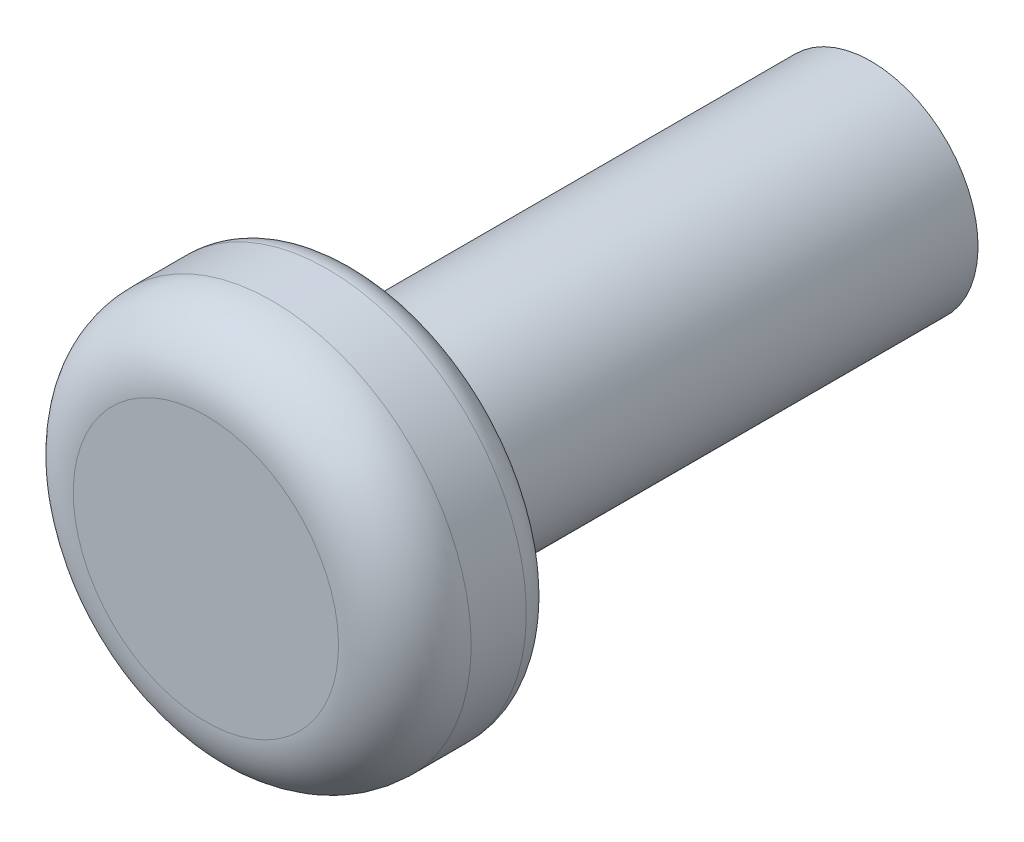
SolidWorks part; units mm, degrees
ref_plane "Front" through (0, 0, 0) normal (0, 0, 1) x (1, 0, 0)
ref_plane "Top" through (0, 0, 0) normal (0, 1, 0) x (1, 0, 0)
ref_plane "Right" through (0, 0, 0) normal (1, 0, 0) x (0, 0, -1)
sketch "Sketch0" plane through (0, 0, 0) normal (1, 0, 0) x (0, 0, -1)
  line L0 (0, 0) -> (-3.55, 0) construction
  line L1 (0, 0) -> (12, 0) construction
  line L2 (-3.55, 4.65) -> (-3.55, -4.65) construction
  line L3 (12, 2.5) -> (12, -2.5) construction
  point P6 (-3.55, 0)
  point P9 (12, 0)
sketch "Sketch1" plane through (0, 0, 0) normal (0, 0, 1) x (1, 0, 0)
  circle A0 centre (0, 0) radius 4.65
extrude "Extrude3" add sketch "Sketch1" along normal up to vertex (3.55 mm away) up to point (0, 0, 3.55)
ref_plane "Plane1" through (0, 0, 3.55) normal (0, 0, 1) x (1, 0, 0)
sketch "Sketch11" plane through (0, 0, 0) normal (1, 0, 0) x (0, 0, -1)
  line L2 (-3.55, 4.65) -> (-3.55, -4.65) construction
  line L4 (0, 4.65) -> (-3.55, 4.65) construction
  line L5 (-2, 4.65) -> (-0.71, 4.65)
  line L6 (0, -4.65) -> (0, 4.65) construction
  line L7 (-3.55, 4.65) -> (-3.55, 3.1) construction
  line L8 (-3.55, 1.55) -> (-3.55, 0) construction
  line L9 (-3.55, 3.1) -> (-3.55, 1.55) construction
  line L10 (-3.55, 3.1) -> (-3.804, 3.1)
  line L11 (0, 0) -> (-3.55, 0) construction
  line L12 (-3.804, 3.1) -> (-3.804, 4.904)
  line L13 (-3.804, 4.904) -> (0.254, 4.904)
  line L14 (0.254, 4.904) -> (0.254, 3.94)
  line L15 (0.254, 3.94) -> (0, 3.94)
  arc A0 (-3.55, 3.1) -> (-2, 4.65) centre (-2, 3.1) cw
  arc A1 (-0.71, 4.65) -> (0, 3.94) centre (-0.71, 3.94) cw
  dimension "D1" = 0.71
  dimension "D2" = 0.254
  dimension "D3" = 0.254
revolve "Cut-Revolve3" cut sketch "Sketch11" angle 360 about L11
sketch "Sketch17" plane through (0, 0, 0) normal (1, 0, 0) x (0, 0, -1)
  line L0 (12, 2.5) -> (12, -2.5) construction
  line L1 (0, 0) -> (12, 0)
  line L2 (0, 0) -> (0, 2.5)
  line L3 (0, 2.5) -> (12, 2.5)
  line L4 (12, 0) -> (12, 2.5)
revolve "Revolve1" add sketch "Sketch17" angle 360 about L11
sketch "Sketch14" plane through (0, 0, 0) normal (1, 0, 0) x (0, 0, -1)
  line L0 (0.0794, 0.5901) -> (0.1786, 0.762) construction
  line L2 (0.1786, 0.762) -> (0.2183, 0.762)
  line L3 (0.2183, 0.762) -> (0.3175, 0.5901) construction
  line L4 (0.3175, 0.5901) -> (0.0794, 0.5901) construction
  line L5 (0.3175, 0.5901) -> (0.3969, 0.5901) construction
  line L6 (0.0794, 0.5901) -> (0, 0.5901) construction
  line L10 (0, 4.65) -> (0, -4.65) construction
  line L11 (0.1786, 0.762) -> (0.0794, 0.5901)
  line L12 (0.0794, 0.5901) -> (0.3175, 0.5901)
  line L13 (0.3175, 0.5901) -> (0.2183, 0.762)
  line L14 (0, 0) -> (-3.55, 0) construction
  line L15 (0, 0) -> (-3.55, 0) construction
  point P11 (0.1984, 0.762)
  dimension "D1" = 60
  dimension "Pitch" = 0.3175
  dimension "D3" = 0.0794
  dimension "D4" = 0.0397
  dimension "Screw Dia" = 1.524
sketch "Sketch15" plane through (0, 0, -12) normal (0, 0, 1) x (1, 0, 0)
  circle A0 centre (0, 0) radius 2.5
  circle A1 centre (0, 0) radius 2.5 construction
curve "Helix/Spiral1" pitch 0.8 height 25.4 turns 31.75 parameters "Pitch"=0.8
ref_axis "Axis1" through (0, 0, 3.3443) along (0, 0, -1)
ref_plane "Contact Surface 1" through (0, 0, 0) normal (0, 0, -1) x (-1, 0, 0)
equation "\"D1@Sketch11\" = \"Head Height@Sketch0\" / 5"
